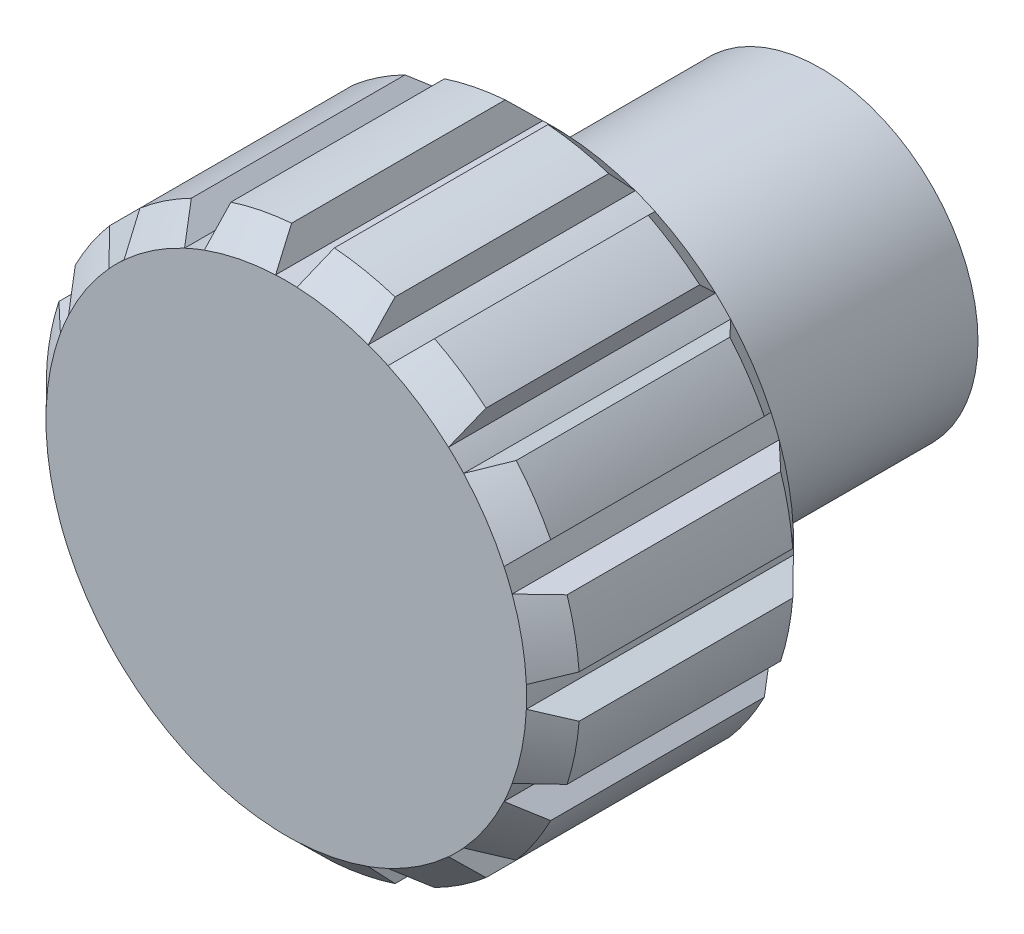
SolidWorks part; units mm, degrees
ref_plane "Front Plane" through (0, 0, 0) normal (0, 0, 1) x (1, 0, 0)
ref_plane "Top Plane" through (0, 0, 0) normal (0, 1, 0) x (1, 0, 0)
ref_plane "Right Plane" through (0, 0, 0) normal (1, 0, 0) x (0, 0, -1)
sketch "Sketch1" plane through (0, 0, 0) normal (0, 0, 1) x (1, 0, 0)
  circle A0 centre (0, 0) radius 3.5
  circle A1 centre (0, 0) radius 7.5
  dimension "D1" = 7
  dimension "D2" = 15
extrude "Boss-Extrude1" add sketch "Sketch1" along normal blind 12.7
sketch "Sketch2" plane through (0, 0, 12.7) normal (0, 0, 1) x (1, 0, 0)
  circle A0 centre (0, 0) radius 12.7
  dimension "D1" = 25.4
extrude "Boss-Extrude2" add sketch "Sketch2" along normal blind 12.7
chamfer "Chamfer1" distance 1.27 angle 45 2 edges at (12.7, 0, 25.4) (12.7, 0, 12.7)
sketch "Sketch3" plane through (0, 0, 25.4) normal (0, 0, 1) x (1, 0, 0)
  line L0 (0, 13.8231) -> (0, 0) construction
  line L1 (-1.4946, 13.8231) -> (-0.508, 11.4187)
  line L2 (1.4946, 13.8231) -> (0.508, 11.4187)
  line L3 (-1.8993, 13.8231) -> (1.9378, 13.8231) construction
  line L4 (-1.4946, 13.8231) -> (1.4946, 13.8231)
  line L5 (3.9091, 13.3428) -> (6.6707, 12.1989)
  line L6 (6.6707, 12.1989) -> (4.8391, 10.3551)
  line L7 (3.9091, 13.3428) -> (3.9004, 10.7439)
  line L8 (8.7176, 10.8312) -> (10.8312, 8.7176)
  line L9 (10.8312, 8.7176) -> (8.4335, 7.715)
  line L10 (8.7176, 10.8312) -> (7.715, 8.4335)
  line L11 (12.1989, 6.6707) -> (13.3428, 3.9091)
  line L12 (13.3428, 3.9091) -> (10.7439, 3.9004)
  line L13 (12.1989, 6.6707) -> (10.3551, 4.8391)
  line L14 (13.8231, 1.4946) -> (13.8231, -1.4946)
  line L15 (13.8231, -1.4946) -> (11.4187, -0.508)
  line L16 (13.8231, 1.4946) -> (11.4187, 0.508)
  line L17 (13.3428, -3.9091) -> (12.1989, -6.6707)
  line L18 (12.1989, -6.6707) -> (10.3551, -4.8391)
  line L19 (13.3428, -3.9091) -> (10.7439, -3.9004)
  line L20 (10.8312, -8.7176) -> (8.7176, -10.8312)
  line L21 (8.7176, -10.8312) -> (7.715, -8.4335)
  line L22 (10.8312, -8.7176) -> (8.4335, -7.715)
  line L23 (6.6707, -12.1989) -> (3.9091, -13.3428)
  line L24 (3.9091, -13.3428) -> (3.9004, -10.7439)
  line L25 (6.6707, -12.1989) -> (4.8391, -10.3551)
  line L26 (1.4946, -13.8231) -> (-1.4946, -13.8231)
  line L27 (-1.4946, -13.8231) -> (-0.508, -11.4187)
  line L28 (1.4946, -13.8231) -> (0.508, -11.4187)
  line L29 (-3.9091, -13.3428) -> (-6.6707, -12.1989)
  line L30 (-6.6707, -12.1989) -> (-4.8391, -10.3551)
  line L31 (-3.9091, -13.3428) -> (-3.9004, -10.7439)
  line L32 (-8.7176, -10.8312) -> (-10.8312, -8.7176)
  line L33 (-10.8312, -8.7176) -> (-8.4335, -7.715)
  line L34 (-8.7176, -10.8312) -> (-7.715, -8.4335)
  line L35 (-12.1989, -6.6707) -> (-13.3428, -3.9091)
  line L36 (-13.3428, -3.9091) -> (-10.7439, -3.9004)
  line L37 (-12.1989, -6.6707) -> (-10.3551, -4.8391)
  line L38 (-13.8231, -1.4946) -> (-13.8231, 1.4946)
  line L39 (-13.8231, 1.4946) -> (-11.4187, 0.508)
  line L40 (-13.8231, -1.4946) -> (-11.4187, -0.508)
  line L41 (-13.3428, 3.9091) -> (-12.1989, 6.6707)
  line L42 (-12.1989, 6.6707) -> (-10.3551, 4.8391)
  line L43 (-13.3428, 3.9091) -> (-10.7439, 3.9004)
  line L44 (-10.8312, 8.7176) -> (-8.7176, 10.8312)
  line L45 (-8.7176, 10.8312) -> (-7.715, 8.4335)
  line L46 (-10.8312, 8.7176) -> (-8.4335, 7.715)
  line L47 (-6.6707, 12.1989) -> (-3.9091, 13.3428)
  line L48 (-3.9091, 13.3428) -> (-3.9004, 10.7439)
  line L49 (-6.6707, 12.1989) -> (-4.8391, 10.3551)
  circle A1 centre (0, 0) radius 11.43 construction
  arc A2 (0.508, 11.4187) -> (-0.508, 11.4187) centre (0, 0) ccw
  arc A3 (4.8391, 10.3551) -> (3.9004, 10.7439) centre (0, 0) ccw
  arc A4 (8.4335, 7.715) -> (7.715, 8.4335) centre (0, 0) ccw
  arc A5 (10.7439, 3.9004) -> (10.3551, 4.8391) centre (0, 0) ccw
  arc A6 (11.4187, -0.508) -> (11.4187, 0.508) centre (0, 0) ccw
  arc A7 (10.3551, -4.8391) -> (10.7439, -3.9004) centre (0, 0) ccw
  arc A8 (7.715, -8.4335) -> (8.4335, -7.715) centre (0, 0) ccw
  arc A9 (3.9004, -10.7439) -> (4.8391, -10.3551) centre (0, 0) ccw
  arc A10 (-0.508, -11.4187) -> (0.508, -11.4187) centre (0, 0) ccw
  arc A11 (-4.8391, -10.3551) -> (-3.9004, -10.7439) centre (0, 0) ccw
  arc A12 (-8.4335, -7.715) -> (-7.715, -8.4335) centre (0, 0) ccw
  arc A13 (-10.7439, -3.9004) -> (-10.3551, -4.8391) centre (0, 0) ccw
  arc A14 (-11.4187, 0.508) -> (-11.4187, -0.508) centre (0, 0) ccw
  arc A15 (-10.3551, 4.8391) -> (-10.7439, 3.9004) centre (0, 0) ccw
  arc A16 (-7.715, 8.4335) -> (-8.4335, 7.715) centre (0, 0) ccw
  arc A17 (-3.9004, 10.7439) -> (-4.8391, 10.3551) centre (0, 0) ccw
  point P72 (0, 0)
  dimension "D1" = 16
  dimension "D2" = 0.508
extrude "Cut-Extrude2" cut sketch "Sketch3" against normal blind 12.7
